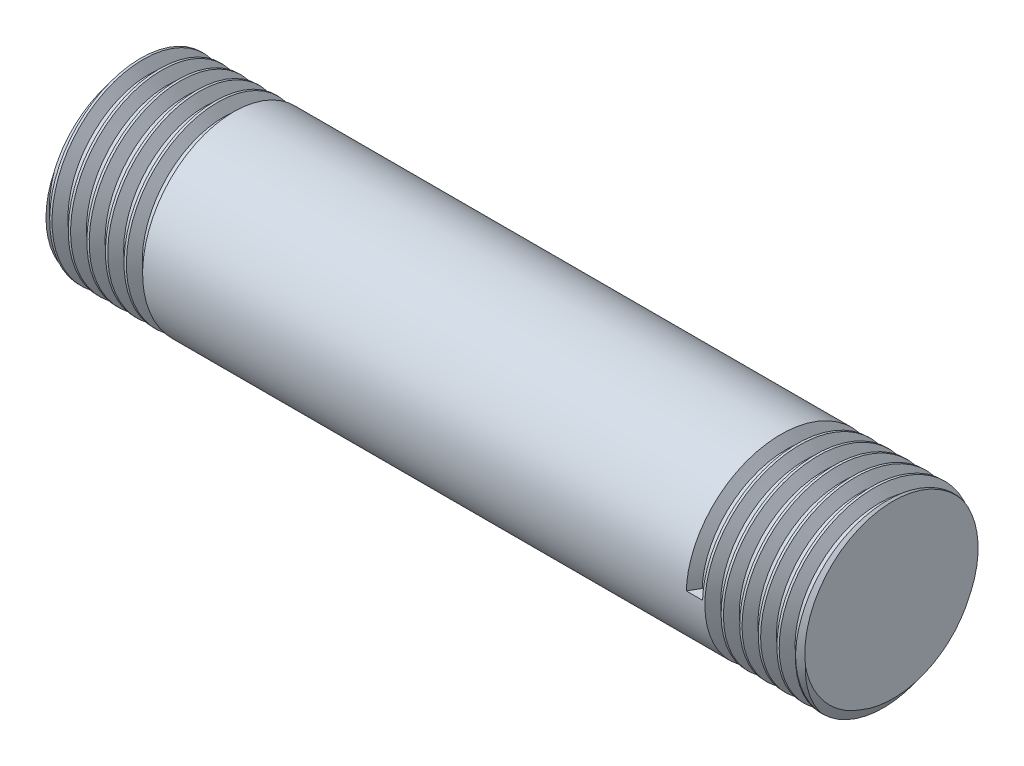
SolidWorks part; units mm, degrees
material "Stainless Steel (ferritic)"
ref_plane "Front Plane" through (0, 0, 0) normal (0, 0, 1) x (1, 0, 0)
ref_plane "Top Plane" through (0, 0, 0) normal (0, 1, 0) x (1, 0, 0)
ref_plane "Right Plane" through (0, 0, 0) normal (1, 0, 0) x (0, 0, -1)
sketch "Sketch5" plane through (0, 0, 0) normal (0, 0, 1) x (1, 0, 0)
  line L0 (0, 0) -> (41, 0)
  dimension "D1" = 41
sweep "Sweep1" add path "Sketch5" circular profile diameter 10 parameters "D3"=10
chamfer "Chamfer1" distance 0.25 angle 45 2 edges at (0, 0, -5) (41, 0, -5)
thread "Thread1" start angle 0, offset 2, length 5, pitch 1, diameter 10
ref_plane "Plane1" through (42.75, 0, 5) normal (0, -1, 0) x (0, 0, 1)
sketch "Thread Profile1" plane through (42.75, 0, 5) normal (0, -1, 0) x (0, 0, 1)
  line L0 (0, 0) -> (0, 1) construction
  line L11 (0, 0) -> (0, 0.875)
  line L12 (0, 0.875) -> (-0.5413, 0.5625)
  line L13 (-0.5413, 0.5625) -> (-0.5413, 0.3125)
  line L15 (-0.5413, 0.3125) -> (0, 0)
  line L17 (-0.5413, 0.4375) -> (0, 0.4375) construction
  point P2 (0, 0)
  dimension "Pitch" = 1
  dimension "Profile_Angle" = 60
  dimension "Profile_Land" = 0.25
  dimension "Profile_Height" = 0.5413
thread "Thread2" pitch 1 profile "Thread Profile2" start angle 0, offset 2, length 5, pitch 1, diameter 10
ref_plane "Plane2" through (-1.75, 0, -5) normal (0, -1, 0) x (0, 0, -1)
sketch "Thread Profile2" plane through (-1.75, 0, -5) normal (0, -1, 0) x (0, 0, -1)
  line L0 (0, 0) -> (0, 1) construction
  line L11 (0, 0) -> (0, 0.875)
  line L12 (0, 0.875) -> (-0.5413, 0.5625)
  line L13 (-0.5413, 0.5625) -> (-0.5413, 0.3125)
  line L15 (-0.5413, 0.3125) -> (0, 0)
  line L17 (-0.5413, 0.4375) -> (0, 0.4375) construction
  point P2 (0, 0)
  dimension "Pitch" = 1
  dimension "Profile_Angle" = 60
  dimension "Profile_Land" = 0.25
  dimension "Profile_Height" = 0.5413
